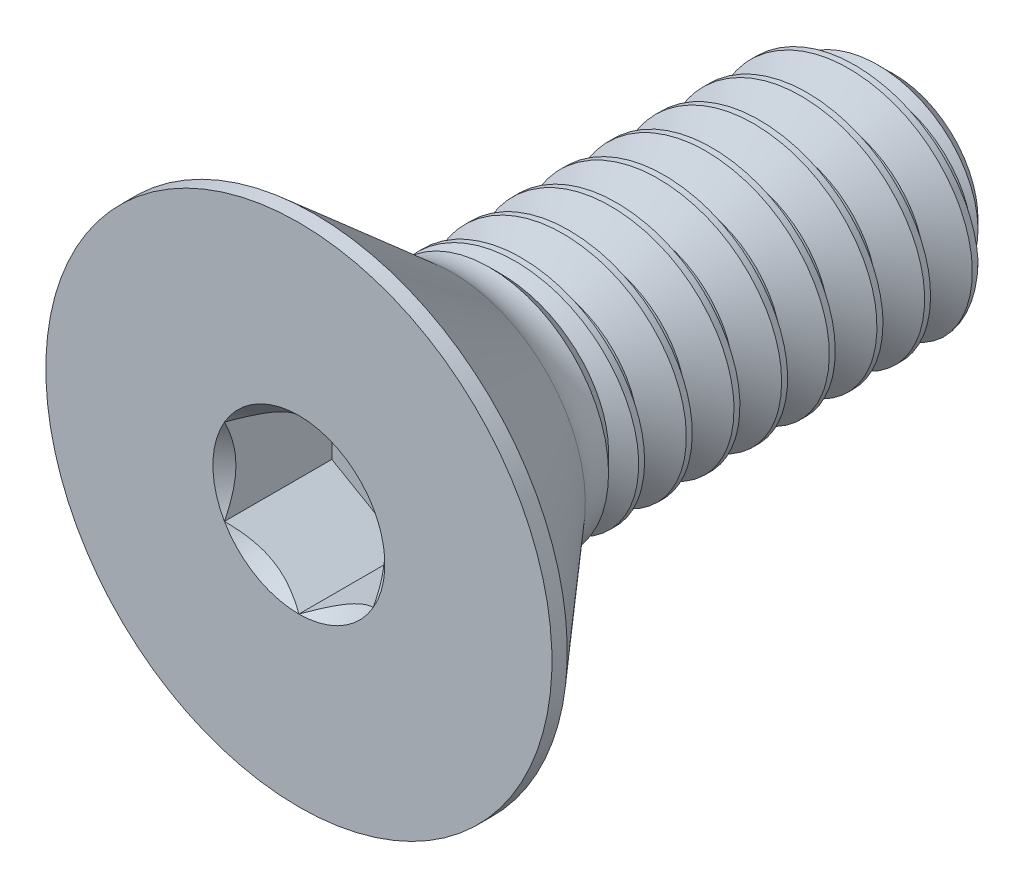
SolidWorks part; units mm, degrees
ref_plane "Front" through (0, 0, 0) normal (0, 0, 1) x (1, 0, 0)
ref_plane "Top" through (0, 0, 0) normal (0, 1, 0) x (1, 0, 0)
ref_plane "Right" through (0, 0, 0) normal (1, 0, 0) x (0, 0, -1)
sketch "Sketch1" plane through (0, 0, 0) normal (1, 0, 0) x (0, 0, -1)
  line L0 (0, 6.7437) -> (0.4089, 6.7437) construction
  line L1 (0.4089, 6.7437) -> (4.0894, 3.5443) construction
  line L2 (0, 3.175) -> (15.875, 3.175)
  line L3 (15.875, 3.175) -> (15.875, 0)
  line L4 (15.875, 0) -> (0, 0)
  line L5 (0, 0) -> (0, 6.7437) construction
  line L6 (0, 6.7437) -> (0, -6.7437) construction
  line L7 (15.875, 3.175) -> (15.875, -3.175) construction
  line L8 (0, -6.7437) -> (0.4089, -6.7437) construction
  line L9 (0.4089, -6.7437) -> (4.0894, -3.5443) construction
  line L11 (0, 3.175) -> (0, 0)
  line L12 (5.0772, 3.175) -> (5.0772, 0) construction
  arc A1 (4.0894, 3.5443) -> (5.0772, 3.175) centre (5.0772, 4.6807) ccw construction
  dimension "D1" = 0.4089
revolve "Revolve1" add sketch "Sketch1" angle 360 mid plane about L4
sketch "Sketch3" plane through (0, 0, -15.875) normal (0, 0, -1) x (-1, 0, 0)
  circle A0 centre (0, 0) radius 3.175
curve "Helix/Spiral1" pitch 1.27 height 15.875 radius 3.175 centre (0, 0, -15.875) axis (0, 0, 1) start towards (0, 1, 0)
sketch "Sketch2" plane through (0, 0, 0) normal (1, 0, 0) x (0, 0, -1)
  line L0 (15.875, 3.175) -> (16.9862, 3.175)
  line L1 (16.9862, 3.175) -> (16.51, 2.3501)
  line L2 (16.51, 2.3501) -> (16.3512, 2.3501)
  line L3 (16.3512, 2.3501) -> (15.875, 3.175)
  line L4 (16.1131, 2.7626) -> (16.7481, 2.7626) construction
  dimension "D1" = 60
  dimension "D2" = 0.1588
  dimension "D3" = 0.635
chamfer "Chamfer1" distance 0.9525 angle 45 1 edges at (0, 3.175, -15.875)
sweep "Cut-Sweep1" cut profiles "Sketch2" path "Helix/Spiral1" align with end faces yes
sketch "Sketch7" plane through (0, 0, 0) normal (1, 0, 0) x (0, 0, -1)
  line L0 (0, 6.7437) -> (0.4089, 6.7437) construction
  line L1 (0.4089, 6.7437) -> (4.0894, 3.5443) construction
  line L2 (0, 6.7437) -> (0.4089, 6.7437)
  line L3 (0.4089, 6.7437) -> (4.0894, 3.5443)
  line L4 (5.0772, 3.175) -> (5.0772, 0) construction
  line L5 (5.0772, 3.175) -> (5.0772, 0)
  line L7 (0, 0) -> (0, 6.7437) construction
  line L8 (0, 0) -> (0, 6.7437)
  line L9 (0, 0) -> (5.0772, 0)
  line L10 (7.4181, 0) -> (-7.4181, 0) construction
  arc A0 (4.0894, 3.5443) -> (5.0772, 3.175) centre (5.0772, 4.6807) ccw construction
  arc A1 (4.0894, 3.5443) -> (5.0772, 3.175) centre (5.0772, 4.6807) ccw
revolve "Revolve2" add sketch "Sketch7" angle 360 mid plane about L9
ref_plane "Plane1" through (0, 0, -5.0772) normal (0, 0, 1) x (1, 0, 0)
sketch "Sketch8" plane through (0, 0, -5.0772) normal (0, 0, 1) x (1, 0, 0)
  circle A0 centre (0, 0) radius 3.175
extrude "Boss-Extrude1" add sketch "Sketch8" against normal through all draft 45
sketch "Sketch5" plane through (0, 0, 0) normal (0, 0, 1) x (1, 0, 0)
  line L1 (1.9844, -1.1457) -> (1.9844, 1.1457)
  line L2 (1.9844, 1.1457) -> (0, 2.2914)
  line L3 (0, 2.2914) -> (-1.9844, 1.1457)
  line L4 (-1.9844, 1.1457) -> (-1.9844, -1.1457)
  line L5 (-1.9844, -1.1457) -> (0, -2.2914)
  line L6 (0, -2.2914) -> (1.9844, -1.1457)
  circle A0 centre (0, 0) radius 1.9844 construction
  dimension "Hex" = 3.9688
extrude "Cut-Extrude2" cut sketch "Sketch5" against normal blind 2.8626
sketch "Sketch6" plane through (0, 0, 0) normal (0, 0, 1) x (1, 0, 0)
  circle A0 centre (0, 0) radius 2.2914
extrude "Cut-Extrude3" cut sketch "Sketch6" against normal through all draft 45
sketch "Sketch9" [suppressed] plane through (0, 0, -5.0772) normal (0, 0, 1) x (1, 0, 0)
  circle A1 centre (0, 0) radius 3.175
  circle A2 centre (0, 0) radius 3.175
  point P0 (0, 3.175)
  dimension "D1" = 0
extrude "Boss-Extrude2" [suppressed] add sketch "Sketch9" against normal offset from surface (13.9728 mm away) 22.225 up to face at (0, 2.2225, -15.875)
sketch "Sketch10" plane through (0, 0, 0) normal (1, 0, 0) x (0, 0, -1)
  line L0 (15.875, 3.175) -> (15.875, -3.175) construction
  point P0 (13.97, -3.175)
  dimension "D1" = 1.905
equation "\"D3@Helix/Spiral1\" = \"Lg@Sketch1\""
equation "\"D2@Sketch2\" = \"D4@Helix/Spiral1\" * .125"
equation "\"D3@Sketch2\" = \"D4@Helix/Spiral1\" * .5"
equation "\"D1@Chamfer1\" = \"D4@Helix/Spiral1\" * .75"
equation "\"D1@Cut-Extrude2\" = \"Head Ht@Sketch1\" * .7"
equation "\"D1@Sketch1\" = \"Head Ht@Sketch1\" * .1"
equation "\"D1@Sketch10\" = \"D4@Helix/Spiral1\" * 1.5"
